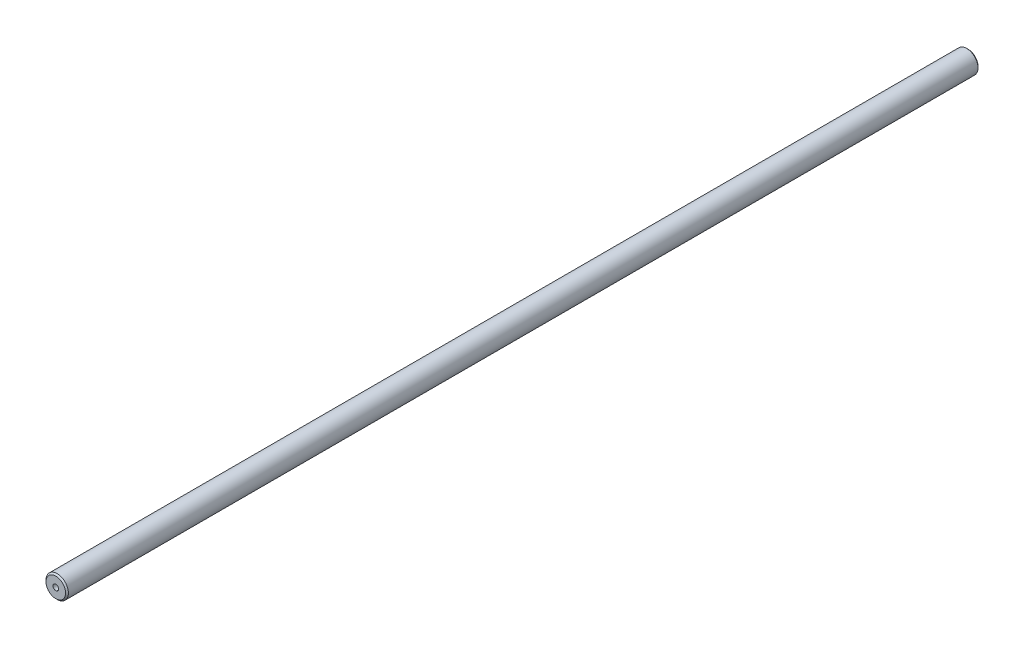
SolidWorks part; units mm, degrees
ref_plane "Front Plane" through (0, 0, 0) normal (0, 0, 1) x (1, 0, 0)
ref_plane "Top Plane" through (0, 0, 0) normal (0, 1, 0) x (1, 0, 0)
ref_plane "Right Plane" through (0, 0, 0) normal (1, 0, 0) x (0, 0, -1)
sketch "Sketch1" plane through (0, 0, 0) normal (0, 0, 1) x (1, 0, 0)
  circle A0 centre (0, 0) radius 4
  dimension "D1" = 8
extrude "Boss-Extrude1" add sketch "Sketch1" along normal blind 326
sketch "Sketch2" plane through (0, 0, 326) normal (0, 0, 1) x (1, 0, 0)
  circle A0 centre (0, 0) radius 1
  dimension "D1" = 2
extrude "Cut-Extrude1" cut sketch "Sketch2" against normal blind 10
chamfer "Chamfer1" distance 0.5 angle 45 2 edges at (4, 0, 0) (4, 0, 326)
